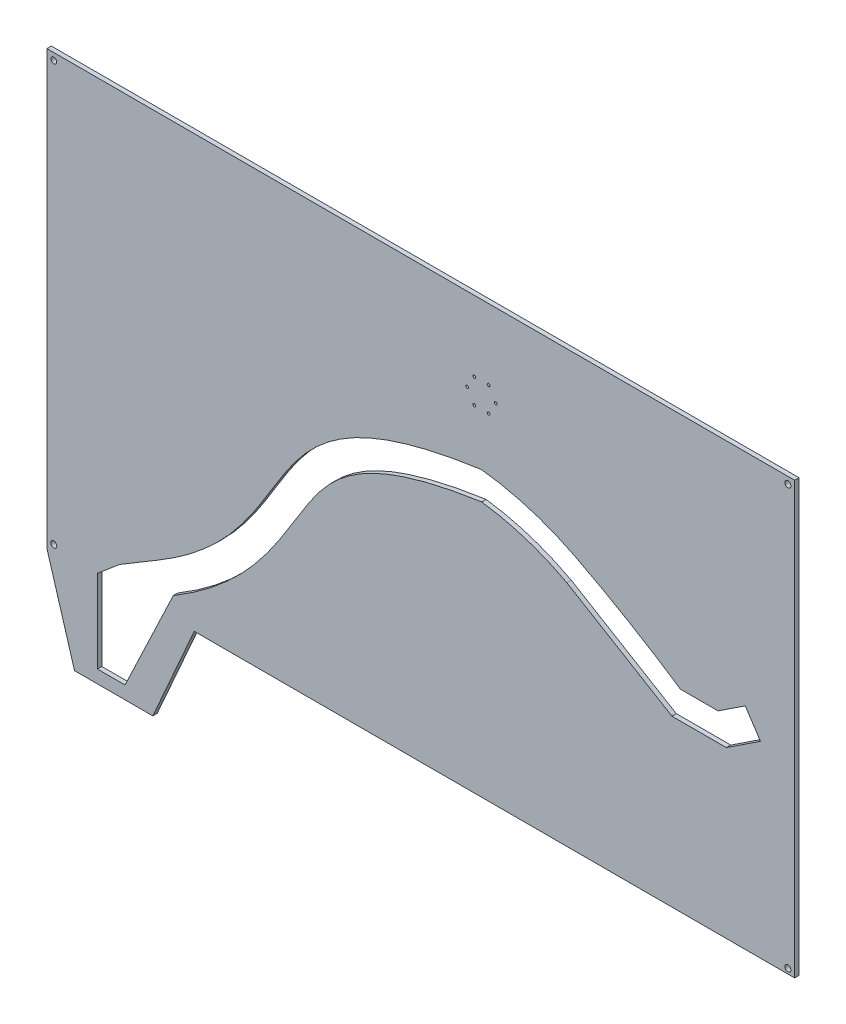
SolidWorks part; units mm, degrees
ref_plane "前视基准面" through (0, 0, 0) normal (0, 0, 1) x (1, 0, 0)
ref_plane "上视基准面" through (0, 0, 0) normal (0, 1, 0) x (1, 0, 0)
ref_plane "右视基准面" through (0, 0, 0) normal (1, 0, 0) x (0, 0, -1)
sketch "Sketch1" plane through (0, 0, 0) normal (0, 0, 1) x (1, 0, 0)
  line L0 (86.3892, 46.5642) -> (136.3892, 46.5642) construction
  line L1 (136.3892, 46.5642) -> (169.6686, 68.4983) construction
  line L2 (-475, -100) -> (-518.0311, -125.7444)
  line L3 (-596.8168, -150) -> (-566.8168, -250)
  line L4 (81.7745, 31.5642) -> (140.8878, 31.5642)
  line L5 (-467.2989, -112.8722) -> (-510.33, -138.6166) construction
  line L6 (140.8878, 31.5642) -> (177.9233, 55.9739)
  line L7 (-459.5978, -125.7444) -> (-511.9755, -236)
  line L8 (-436.8168, -147.9944) -> (215.0808, -147.9944)
  line L9 (215.0808, -147.9944) -> (215.0808, 320)
  line L10 (215.0808, 320) -> (-596.8168, 320)
  line L11 (-596.8168, -150) -> (-596.8168, 320)
  line L12 (215.0808, -147.9944) -> (-596.8168, 320) construction
  line L13 (215.0808, 320) -> (-596.8168, -150) construction
  line L14 (-518.0311, -125.7444) -> (-459.5978, -125.7444) construction
  line L15 (-436.8168, -147.9944) -> (-481.8168, -250)
  line L16 (-566.8168, -250) -> (-481.8168, -250)
  line L17 (90.9712, 61.5642) -> (131.8907, 61.5642)
  line L18 (-511.9755, -236) -> (-541.9755, -236)
  line L19 (-541.9755, -236) -> (-541.9755, -146)
  line L20 (-518.0311, -125.7444) -> (-541.9755, -146)
  line L21 (-32.3237, 100) -> (135.1953, 100) construction
  line L22 (-25, 130) -> (125, 130) construction
  line L23 (-28.6108, 115) -> (130.0228, 115) construction
  line L24 (131.8907, 61.5642) -> (161.4139, 81.0227)
  line L25 (177.9233, 55.9739) -> (161.4139, 81.0227)
  line L26 (-21.7014, 128.3139) -> (-25, 130)
  line L27 (-32.3237, 100) -> (81.7745, 31.5642)
  arc A0 (-125, 160) -> (-25, 130) centre (-159.8893, -137.9643) cw
  arc A1 (-28.6108, 115) -> (86.3892, 46.5642) centre (-559.3589, -907.7137) cw construction
  arc A2 (-124.7147, 129.7347) -> (-32.3237, 100) centre (-159.8893, -137.9643) cw
  circle A3 centre (-125, 230) radius 15.5 construction
  arc A4 (-124.84, 144.8723) -> (-28.6108, 115) centre (-159.8893, -137.9643) cw construction
  arc A5 (-21.7014, 128.3139) -> (90.9712, 61.5642) centre (-559.3589, -907.7137) cw
  circle A6 centre (-589.3757, -142.5578) radius 3.2924
  circle A7 centre (207.6422, -142.5578) radius 3.2924
  circle A8 centre (207.6422, 312.5578) radius 3.2944
  circle A9 centre (-589.3757, 312.5578) radius 3.1635
  arc A10 (135.1953, 100) -> (187.8618, 132.897) centre (303.6181, -111.0302) cw construction
  arc A11 (130.0228, 115) -> (181.4309, 146.4485) centre (303.6181, -111.0302) cw construction
  arc A12 (125, 130) -> (175, 160) centre (303.6181, -111.0302) cw construction
  arc A13 (-35.5202, 101.6861) -> (81.7745, 31.5642) centre (-559.3589, -907.7137) cw construction
  circle A14 centre (-140.5, 230) radius 1.5
  circle A15 centre (-132.75, 243.4234) radius 1.5
  circle A16 centre (-117.25, 243.4234) radius 1.5
  circle A17 centre (-109.5, 230) radius 1.5
  circle A18 centre (-117.25, 216.5766) radius 1.5
  circle A19 centre (-132.75, 216.5766) radius 1.5
  spline S0 degree 3 poles (-475, -100) (-419.5406, -66.8201) (-329.5908, 43.116) (-307.6356, 134.2871) (-125, 160) knots 0 0 0 0 0.312224 1 1 1 1
  spline S1 degree 1 poles (-459.5978, -125.7444) (-124.7147, 129.7347) knots 0 0 1 1 construction
  spline S2 degree 3 poles (-459.5978, -125.7444) (-458.1292, -124.8657) (-455.1858, -123.0815) (-449.4714, -119.5247) (-442.5555, -115.0462) (-434.6362, -109.6397) (-424.5564, -102.3861) (-412.8294, -93.2453) (-400.0558, -82.1905) (-388.4865, -71.0922) (-374.5374, -56.3046) (-359.6201, -37.9792) (-344.8908, -16.7676) (-332.3401, 3.2457) (-321.0552, 21.7964) (-310.226, 38.6648) (-299.0796, 53.8348) (-286.8128, 67.5146) (-272.4318, 80.0885) (-257.6527, 89.9241) (-243.4982, 97.442) (-231.5651, 102.8866) (-218.1727, 108.1127) (-203.191, 113.0878) (-189.2817, 116.9961) (-177.2434, 119.9629) (-167.7458, 122.1041) (-157.766, 124.1573) (-149.0369, 125.7919) (-141.7993, 127.0518) (-136.2431, 127.9723) (-131.5022, 128.7191) (-127.6487, 129.3032) (-125.6903, 129.5925) (-124.7147, 129.7347) knots 0 0 0 0 0.007773 0.015545 0.03109 0.046636 0.062181 0.093271 0.124361 0.155452 0.186542 0.248723 0.310904 0.373084 0.435265 0.497446 0.559626 0.621807 0.683988 0.746169 0.777259 0.808349 0.83944 0.87053 0.90162 0.917166 0.932711 0.948256 0.963801 0.971574 0.979346 0.987119 0.991005 0.994892 0.994892 0.994892 0.994892
  spline S3 degree 1 poles (-467.2989, -112.8722) (-124.84, 144.8723) knots 0 0 1 1 construction
  spline S4 degree 3 poles (-467.2989, -112.8722) (-465.8766, -112.0213) (-463.025, -110.2926) (-457.4973, -106.8516) (-450.8174, -102.5249) (-443.1848, -97.3122) (-433.4896, -90.3317) (-422.2436, -81.559) (-410.0336, -70.981) (-398.9994, -60.3828) (-385.707, -46.2708) (-371.4731, -28.7597) (-357.2741, -8.2881) (-344.9599, 11.3612) (-333.6257, 29.9919) (-322.417, 47.4318) (-310.4985, 63.6121) (-297.0179, 78.5777) (-281.0248, 92.4603) (-264.7088, 103.2127) (-249.3105, 111.3089) (-236.4572, 117.1105) (-222.1723, 122.621) (-206.3349, 127.8161) (-191.7467, 131.8615) (-179.1859, 134.915) (-169.3063, 137.1107) (-158.9544, 139.2089) (-149.9221, 140.8739) (-142.4479, 142.1541) (-136.7117, 143.0887) (-130.8627, 143.9946) (-126.8382, 144.5862) (-124.84, 144.8723) knots 0 0 0 0 0.007793 0.015586 0.031173 0.046759 0.062345 0.093518 0.12469 0.155863 0.187036 0.249381 0.311726 0.374071 0.436417 0.498762 0.561107 0.623452 0.685798 0.748143 0.779315 0.810488 0.841661 0.872833 0.904006 0.919592 0.935179 0.950765 0.966351 0.974144 0.981937 0.989731 0.997524 0.997524 0.997524 0.997524 construction
  point P38 (-190, 85.5025)
  point P62 (-125, 230)
  dimension "D5" = 300
  dimension "D8" = 15
  dimension "D14" = 470
  dimension "D18" = 30
  dimension "D19" = 30
  dimension "D20" = 90
  dimension "D21" = 85
  dimension "D22" = 651.8975
  dimension "D23" = 70
  dimension "D24" = 100
  dimension "D26" = 6
  dimension "D27" = 3
  dimension "D1" = 105
  dimension "D2" = 100
  dimension "D3" = 350
  dimension "D4" = 260
  dimension "D6" = 100
  dimension "D7" = 30
  dimension "D9" = 15
  dimension "D10" = 115
  dimension "D11" = 50
  dimension "D13" = 15
  dimension "D15" = 190
  dimension "D16" = 320
  dimension "D17" = 100
  dimension "D25" = 811.9
  dimension "D12" = 30
extrude "Boss-Extrude1" add sketch "Sketch1" along normal blind 4.7625
